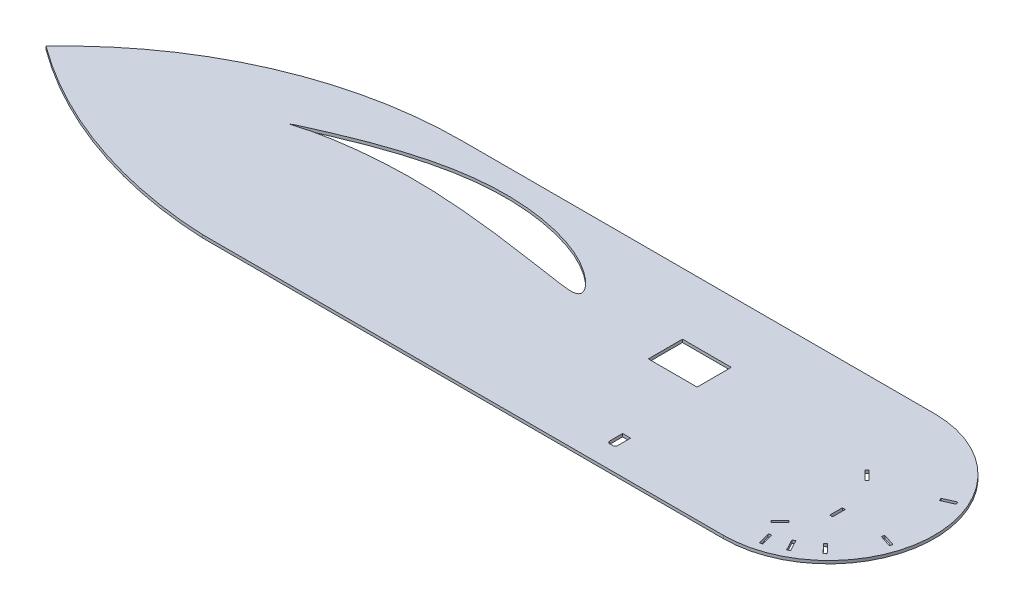
SolidWorks part; units mm, degrees
ref_plane "Front Plane" through (0, 0, 0) normal (0, 0, 1) x (1, 0, 0)
ref_plane "Top Plane" through (0, 0, 0) normal (0, 1, 0) x (1, 0, 0)
ref_plane "Right Plane" through (0, 0, 0) normal (1, 0, 0) x (0, 0, -1)
sketch "Sketch1" plane through (0, 0, 0) normal (0, 1, 0) x (1, 0, 0)
  line L0 (800, 108) -> (0, 108) construction
  line L1 (266.4083, 0) -> (800, 0)
  line L2 (0, 0) -> (0, 216) construction
  line L3 (316.2946, 216) -> (800, 216)
  line L7 (247.07, 156) -> (658.07, 156) construction
  arc A0 (800, 216) -> (800, 0) centre (800, 108) cw
  arc A2 (266.4083, 0) -> (19.4291, 86.8932) centre (286.1808, 450.645) cw
  arc A4 (19.4291, 86.8932) -> (316.2946, 216) centre (316.2946, -189.8565) cw
  dimension "D1" = 800
  dimension "D2" = 60
extrude "Boss-Extrude1" add sketch "Sketch1" along normal blind 3
sketch "Sketch2" plane through (0, 0, 0) normal (0, -1, 0) x (1, 0, 0)
  line L0 (605.07, -153) -> (605.07, 81) construction
  line L1 (655.07, -153) -> (605.07, -153)
  line L2 (655.07, -153) -> (655.07, -118)
  line L3 (655.07, -118) -> (605.07, -118)
  line L4 (823.6893, -121.2328) -> (814.4969, -130.4252)
  line L5 (814.4969, -130.4252) -> (816.6182, -132.5465)
  line L6 (816.6182, -132.5465) -> (825.8106, -123.3541)
  line L7 (825.8106, -123.3541) -> (823.6893, -121.2328)
  line L8 (823.6893, -121.2328) -> (814.4969, -130.4252)
  line L9 (814.4969, -130.4252) -> (816.6182, -132.5465)
  line L10 (816.6182, -132.5465) -> (825.8106, -123.3541)
  line L11 (825.8106, -123.3541) -> (823.6893, -121.2328)
  line L12 (605.07, -153) -> (605.07, -118)
  line L20 (824.4999, -25.0394) -> (827.9651, -12.5098)
  line L21 (827.9651, -12.5098) -> (825.0736, -11.7101)
  line L22 (825.0736, -11.7101) -> (821.6084, -24.2398)
  line L23 (821.6084, -24.2398) -> (824.4999, -25.0394)
  line L24 (824.4999, -25.0394) -> (827.9651, -12.5098)
  line L25 (827.9651, -12.5098) -> (825.0736, -11.7101)
  line L26 (825.0736, -11.7101) -> (821.6084, -24.2398)
  line L27 (821.6084, -24.2398) -> (824.4999, -25.0394)
  line L28 (839.4566, -85.3169) -> (839.4566, -72.3169)
  line L29 (839.4566, -72.3169) -> (836.4566, -72.3169)
  line L30 (836.4566, -72.3169) -> (836.4566, -85.3169)
  line L31 (836.4566, -85.3169) -> (839.4566, -85.3169)
  line L32 (839.4566, -85.3169) -> (839.4566, -72.3169)
  line L33 (839.4566, -72.3169) -> (836.4566, -72.3169)
  line L34 (836.4566, -72.3169) -> (836.4566, -85.3169)
  line L35 (836.4566, -85.3169) -> (839.4566, -85.3169)
  line L37 (212.57, -142.2618) -> (212.57, -142.2948)
  line L38 (212.57, -142.2618) -> (212.57, -142.2948)
  line L40 (658.07, -25.4734) -> (658.07, -38.6734)
  line L41 (663.77, -22.9734) -> (660.57, -22.9734)
  line L42 (666.27, -38.6734) -> (666.27, -25.4734)
  line L43 (658.07, -38.6734) -> (666.27, -38.6734)
  line L44 (658.07, -25.4734) -> (658.07, -38.6734)
  line L45 (663.77, -22.9734) -> (660.57, -22.9734)
  line L46 (666.27, -38.6734) -> (666.27, -25.4734)
  line L47 (658.07, -38.6734) -> (666.27, -38.6734)
  line L188 (878.5445, -144.2417) -> (890.4412, -149.4828) construction
  line L189 (890.4412, -149.4828) -> (891.6506, -146.7374) construction
  line L190 (891.6506, -146.7374) -> (879.7539, -141.4964) construction
  line L191 (879.7539, -141.4964) -> (878.5445, -144.2417) construction
  line L192 (882.6974, -82.6259) -> (895.0575, -78.5976) construction
  line L193 (895.0575, -78.5976) -> (894.1279, -75.7453) construction
  line L194 (894.1279, -75.7453) -> (881.7678, -79.7735) construction
  line L195 (881.7678, -79.7735) -> (882.6974, -82.6259) construction
  line L196 (860.5359, -46.2092) -> (869.4711, -36.7667) construction
  line L197 (869.4711, -36.7667) -> (867.2921, -34.7047) construction
  line L198 (867.2921, -34.7047) -> (858.3569, -44.1473) construction
  line L199 (858.3569, -44.1473) -> (860.5359, -46.2092) construction
  line L200 (841.855, -32.2976) -> (847.947, -20.8133) construction
  line L201 (847.947, -20.8133) -> (845.2968, -19.4075) construction
  line L202 (845.2968, -19.4075) -> (839.2048, -30.8918) construction
  line L203 (839.2048, -30.8918) -> (841.855, -32.2976) construction
  line L204 (822.4089, -44.7346) -> (813.2165, -35.5422) construction
  line L205 (813.2165, -35.5422) -> (811.0952, -37.6635) construction
  line L206 (811.0952, -37.6635) -> (820.2876, -46.8559) construction
  line L207 (820.2876, -46.8559) -> (822.4089, -44.7346) construction
  line L208 (878.5445, -144.2417) -> (890.4412, -149.4828)
  line L209 (890.4412, -149.4828) -> (891.6506, -146.7374)
  line L210 (891.6506, -146.7374) -> (879.7539, -141.4964)
  line L211 (879.7539, -141.4964) -> (878.5445, -144.2417)
  line L212 (882.6974, -82.6259) -> (895.0575, -78.5976)
  line L213 (895.0575, -78.5976) -> (894.1279, -75.7453)
  line L214 (894.1279, -75.7453) -> (881.7678, -79.7735)
  line L215 (881.7678, -79.7735) -> (882.6974, -82.6259)
  line L216 (860.5359, -46.2092) -> (869.4711, -36.7667)
  line L217 (869.4711, -36.7667) -> (867.2921, -34.7047)
  line L218 (867.2921, -34.7047) -> (858.3569, -44.1473)
  line L219 (858.3569, -44.1473) -> (860.5359, -46.2092)
  line L220 (841.855, -32.2976) -> (847.947, -20.8133)
  line L221 (847.947, -20.8133) -> (845.2968, -19.4075)
  line L222 (845.2968, -19.4075) -> (839.2048, -30.8918)
  line L223 (839.2048, -30.8918) -> (841.855, -32.2976)
  line L224 (822.4089, -44.7346) -> (813.2165, -35.5422)
  line L225 (813.2165, -35.5422) -> (811.0952, -37.6635)
  line L226 (811.0952, -37.6635) -> (820.2876, -46.8559)
  line L227 (820.2876, -46.8559) -> (822.4089, -44.7346)
  arc A2 (660.57, -22.9734) -> (658.07, -25.4734) centre (660.57, -25.4734) ccw
  arc A3 (666.27, -25.4734) -> (663.77, -22.9734) centre (663.77, -25.4734) ccw
  arc A4 (660.57, -22.9734) -> (658.07, -25.4734) centre (660.57, -25.4734) ccw
  arc A5 (666.27, -25.4734) -> (663.77, -22.9734) centre (663.77, -25.4734) ccw
  spline S1 degree 3 poles (-935.9633, -1778.8288) (190.5889, -95.3438) (194.6064, -131.763) (215.6642, -144.2206) (218.7234, -145.7779) (222.7838, -147.5804) (227.7591, -149.7808) (233.6732, -152.3729) (243.3346, -156.474) (254.0716, -160.9286) (265.8113, -165.5514) (275.5598, -169.1926) (285.8203, -172.7897) (300.2132, -177.4429) (315.0475, -181.6144) (330.2168, -185.0782) (341.7168, -187.2628) (353.2384, -188.9705) (364.7498, -190.1898) (376.2222, -190.8893) (387.6115, -191.0869) (398.8538, -190.7647) (413.4214, -189.6963) (427.5808, -187.7) (441.1954, -184.8275) (450.8219, -182.3197) (459.9489, -179.4697) (468.5117, -176.2876) (476.4536, -172.8247) (483.7151, -169.1289) (490.2481, -165.2848) (496.0197, -161.4069) (500.998, -157.5857) (505.1476, -153.8841) (508.4473, -150.3827) (510.8522, -147.1808) (512.2305, -144.519) (512.6724, -142.438) (512.366, -140.694) (510.8363, -139.2679) (508.3008, -138.6046) (504.9907, -138.3969) (500.8451, -138.6329) (495.8864, -139.207) (490.1274, -140.0338) (483.6007, -141.0142) (476.346, -142.082) (468.4189, -143.2709) (459.8696, -144.553) (447.4042, -146.414) (434.3028, -148.292) (413.2306, -151.0803) (394.9165, -153.1705) (372.4131, -155.1852) (353.2786, -156.4974) (334.1039, -157.1205) (318.8375, -157.1193) (307.5693, -156.8631) (296.5448, -156.3424) (285.8536, -155.5986) (275.5863, -154.6546) (265.8296, -153.5569) (256.6735, -152.3128) (248.205, -150.9585) (240.5101, -149.5233) (233.6661, -148.0641) (227.7356, -146.6296) (222.7715, -145.2056) (218.7746, -143.9126) (215.7248, -142.9952) (193.3721, -137.343) (166.6151, -157.487) (567.9657, 1824.9991) knots -0.10608 -0.10608 -0.10608 -0.10608 0.001413 0.005226 0.010781 0.017816 0.026461 0.036791 0.048686 0.076639 0.092363 0.109003 0.126387 0.144339 0.181313 0.200023 0.218713 0.237261 0.255692 0.274037 0.292193 0.310133 0.327788 0.362002 0.378421 0.394287 0.409543 0.424114 0.437938 0.450942 0.463044 0.474154 0.484165 0.493024 0.500713 0.507126 0.51213 0.514904 0.517171 0.520262 0.524245 0.529498 0.536092 0.544061 0.553363 0.563905 0.575615 0.58842 0.602227 0.616944 0.648676 0.665501 0.718564 0.736789 0.773513 0.810245 0.828489 0.846493 0.864125 0.881249 0.897725 0.913415 0.928184 0.941897 0.954411 0.965603 0.97535 0.983576 0.990285 0.995433 0.9988 1.100441 1.100441 1.100441 1.100441 only from (212.57, -142.2948) to (212.57, -142.2618)
  spline S2 degree 3 poles (212.57, -142.2948) (212.8151, -142.4601) (213.7215, -143.0713) (215.6642, -144.2206) (218.7234, -145.7779) (222.7838, -147.5804) (227.7591, -149.7808) (233.6732, -152.3729) (243.3346, -156.474) (254.0716, -160.9286) (265.8113, -165.5514) (275.5598, -169.1926) (285.8203, -172.7897) (300.2132, -177.4429) (315.0475, -181.6144) (330.2168, -185.0782) (341.7168, -187.2628) (353.2384, -188.9705) (364.7498, -190.1898) (376.2222, -190.8893) (387.6115, -191.0869) (398.8538, -190.7647) (413.4214, -189.6963) (427.5808, -187.7) (441.1954, -184.8275) (450.8219, -182.3197) (459.9489, -179.4697) (468.5117, -176.2876) (476.4536, -172.8247) (483.7151, -169.1289) (490.2481, -165.2848) (496.0197, -161.4069) (500.998, -157.5857) (505.1476, -153.8841) (508.4473, -150.3827) (510.8522, -147.1808) (512.2305, -144.519) (512.6724, -142.438) (512.366, -140.694) (510.8363, -139.2679) (508.3008, -138.6046) (504.9907, -138.3969) (500.8451, -138.6329) (495.8864, -139.207) (490.1274, -140.0338) (483.6007, -141.0142) (476.346, -142.082) (468.4189, -143.2709) (459.8696, -144.553) (447.4042, -146.414) (434.3028, -148.292) (413.2306, -151.0803) (394.9165, -153.1705) (372.4131, -155.1852) (353.2786, -156.4974) (334.1039, -157.1205) (318.8375, -157.1193) (307.5693, -156.8631) (296.5448, -156.3424) (285.8536, -155.5986) (275.5863, -154.6546) (265.8296, -153.5569) (256.6735, -152.3128) (248.205, -150.9585) (240.5101, -149.5233) (233.6661, -148.0641) (227.7356, -146.6296) (222.7715, -145.2056) (218.7746, -143.9126) (215.7248, -142.9952) (213.7534, -142.4967) (212.8162, -142.3107) (212.57, -142.2618) knots 0 0 0 0 0.001413 0.005226 0.010781 0.017816 0.026461 0.036791 0.048686 0.076639 0.092363 0.109003 0.126387 0.144339 0.181313 0.200023 0.218713 0.237261 0.255692 0.274037 0.292193 0.310133 0.327788 0.362002 0.378421 0.394287 0.409543 0.424114 0.437938 0.450942 0.463044 0.474154 0.484165 0.493024 0.500713 0.507126 0.51213 0.514904 0.517171 0.520262 0.524245 0.529498 0.536092 0.544061 0.553363 0.563905 0.575615 0.58842 0.602227 0.616944 0.648676 0.665501 0.718564 0.736789 0.773513 0.810245 0.828489 0.846493 0.864125 0.881249 0.897725 0.913415 0.928184 0.941897 0.954411 0.965603 0.97535 0.983576 0.990285 0.995433 0.9988 1 1 1 1
  dimension "D6" = 35
  dimension "D1" = 0
  dimension "D2" = 0
  dimension "D3" = 0
  dimension "D4" = 0
  dimension "D5" = 0
extrude "Cut-Extrude1" cut sketch "Sketch2" against normal through all
